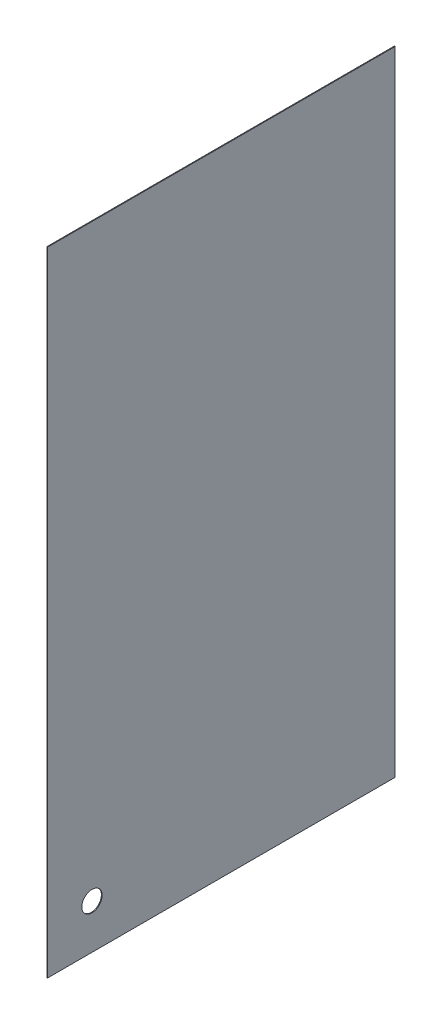
SolidWorks part; units mm, degrees
ref_plane "Front Plane" through (0, 0, 0) normal (0, 0, 1) x (1, 0, 0)
ref_plane "Top Plane" through (0, 0, 0) normal (0, 1, 0) x (1, 0, 0)
ref_plane "Right Plane" through (0, 0, 0) normal (1, 0, 0) x (0, 0, -1)
sketch "BaseFlange" plane through (0, 0, 0) normal (1, 0, 0) x (0, 0, -1)
  line L1 (548, 998) -> (0, 998)
  line L2 (548, 998) -> (548, 0)
  line L3 (548, 0) -> (0, 0)
  line L4 (0, 998) -> (0, 0)
  point P0 (0, 0)
  dimension "Depth" = 548
  dimension "Height" = 998
base flange "Base-Flange1" sketch "BaseFlange" thickness 1.2 reverse thickness direction yes parameters "D1"=1
sketch "Sketch3" plane through (1.2, 0, 0) normal (1, 0, 0) x (0, 0, -1)
  line L0 (0, 998) -> (0, 0) construction
  line L1 (0, 0) -> (548, 0) construction
  circle A0 centre (70, 70) radius 16
  dimension "D1" = 70
  dimension "D3" = 32
  dimension "D2" = 70
extrude "Cut-Extrude2" cut sketch "Sketch3" against normal blind 10
sketch "Bend-Lines1" [suppressed] plane through (0, 0, 0) normal (0, 1, 0) x (1, 0, 0)
sketch "Bounding-Box1" [suppressed] plane through (0, 0, 0) normal (0, 1, 0) x (1, 0, 0)
sheet metal parameters "Sheet-Metal1" thickness 1.2 parameters "D1"=1
flat pattern "Flat-Pattern1" [suppressed]
sketch "Bend-Lines2" plane through (0, 0, 0) normal (0, 1, 0) x (1, 0, 0)
sketch3d "Bounding-Box2" [suppressed]
  line L0 (0, 998, 0) -> (0, 0, 0) construction
  line L1 (-548, 998, 0) -> (-548, 0, 0) construction
  line L2 (0, 998, 0) -> (-548, 998, 0) construction
  line L3 (0, 0, 0) -> (-548, 0, 0) construction
sheet metal parameters "Sheet-Metal3" thickness 1.2 parameters "D1"=1
flat pattern "Flat-Pattern1"
sketch "Bend-Lines2" plane through (0, 0, 0) normal (0, 1, 0) x (1, 0, 0)
sketch3d "Bounding-Box2" [suppressed]
  line L0 (0, 998, 0) -> (0, 0, 0) construction
  line L1 (-548, 998, 0) -> (-548, 0, 0) construction
  line L2 (0, 998, 0) -> (-548, 998, 0) construction
  line L3 (0, 0, 0) -> (-548, 0, 0) construction
